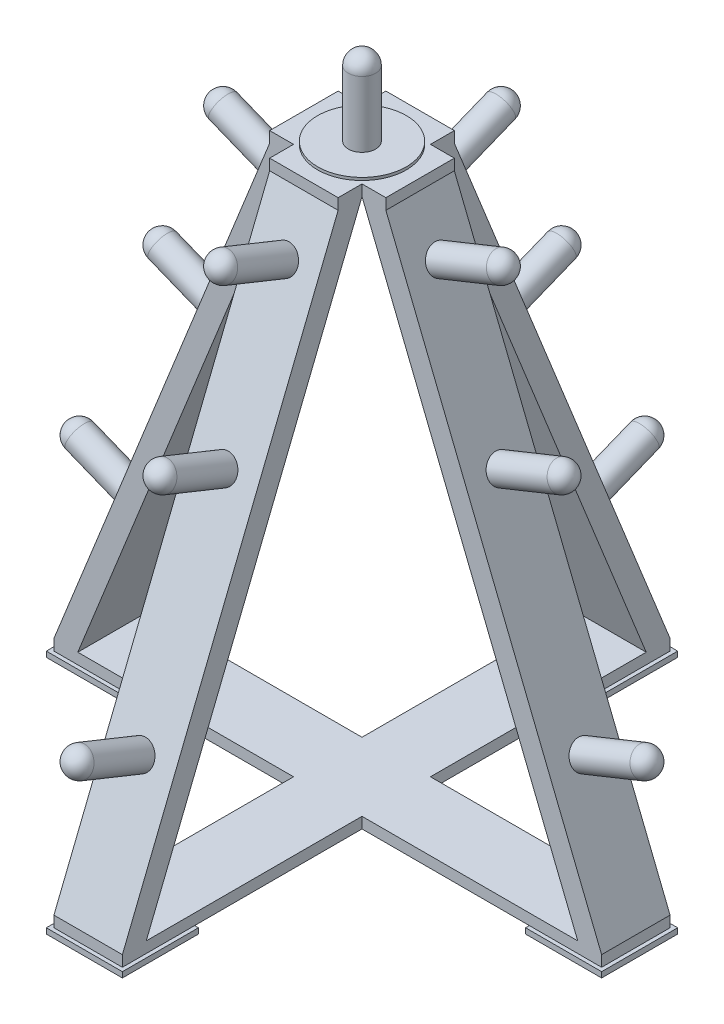
SolidWorks part; units mm, degrees
ref_plane "Front Plane" through (0, 0, 0) normal (0, 0, 1) x (1, 0, 0)
ref_plane "Top Plane" through (0, 0, 0) normal (0, 1, 0) x (1, 0, 0)
ref_plane "Right Plane" through (0, 0, 0) normal (1, 0, 0) x (0, 0, -1)
sketch "Sketch1" plane through (0, 0, 0) normal (0, 1, 0) x (1, 0, 0)
  line L0 (500, 62.5) -> (62.5, 62.5)
  line L1 (-62.5, 500) -> (62.5, 500)
  line L2 (-62.5, 500) -> (-62.5, 62.5)
  line L3 (-62.5, -500) -> (62.5, -500)
  line L4 (62.5, 500) -> (62.5, 62.5)
  line L7 (500, 62.5) -> (500, -62.5)
  line L8 (500, -62.5) -> (62.5, -62.5)
  line L9 (-500, 62.5) -> (-500, -62.5)
  line L10 (-62.5, -62.5) -> (-500, -62.5)
  line L11 (-62.5, 62.5) -> (-500, 62.5)
  line L13 (-62.5, -62.5) -> (-62.5, -500)
  line L14 (62.5, -62.5) -> (62.5, -500)
  point P0 (0, 0)
  point P13 (500, 0)
  dimension "D1" = 125
  dimension "D2" = 1000
extrude "Boss-Extrude1" add sketch "Sketch1" along normal blind 20
ref_plane "Plane1" through (0, 1000, 0) normal (0, 1, 0) x (1, 0, 0)
sketch "Sketch2" plane through (0, 1000, 0) normal (0, 1, 0) x (1, 0, 0)
  line L0 (-62.5, 106.087) -> (-62.5, 62.5)
  line L1 (-62.5, 500) -> (-62.5, 62.5) construction
  line L2 (-62.5, 62.5) -> (-106.087, 62.5)
  line L3 (-62.5, 62.5) -> (-500, 62.5) construction
  line L4 (-106.087, 62.5) -> (-106.087, -62.5)
  line L5 (-500, -62.5) -> (-62.5, -62.5) construction
  line L6 (-106.087, -62.5) -> (-62.5, -62.5)
  line L7 (-62.5, -62.5) -> (-62.5, -106.087)
  line L8 (-62.5, -62.5) -> (-62.5, -500) construction
  line L9 (-62.5, -106.087) -> (62.5, -106.087)
  line L10 (62.5, -500) -> (62.5, -62.5) construction
  line L11 (62.5, -106.087) -> (62.5, -62.5)
  line L12 (62.5, -62.5) -> (106.087, -62.5)
  line L13 (62.5, -62.5) -> (500, -62.5) construction
  line L14 (106.087, -62.5) -> (106.087, 62.5)
  line L15 (500, 62.5) -> (62.5, 62.5) construction
  line L16 (106.087, 62.5) -> (62.5, 62.5)
  line L17 (62.5, 62.5) -> (62.5, 106.087)
  line L18 (62.5, 62.5) -> (62.5, 500) construction
  line L19 (62.5, 106.087) -> (-62.5, 106.087)
sketch "Sketch3" plane through (0, 20, 0) normal (0, 1, 0) x (1, 0, 0)
  line L0 (-500, -62.5) -> (-62.5, -62.5) construction
  line L1 (-500, 62.5) -> (-456.413, 62.5)
  line L2 (-500, 62.5) -> (-500, -62.5)
  line L3 (-500, -62.5) -> (-456.413, -62.5)
  line L4 (-456.413, 62.5) -> (-456.413, -62.5)
  line L6 (-62.5, 62.5) -> (-106.087, 62.5) construction
extrude "Boss-Extrude2" add sketch "Sketch2" along normal blind 20 separate body
sketch "Sketch4" plane through (0, 1000, 0) normal (0, 1, 0) x (1, 0, 0)
  line L1 (-106.087, 62.5) -> (-62.5, 62.5)
  line L2 (-106.087, 62.5) -> (-106.087, -62.5)
  line L3 (-106.087, -62.5) -> (-62.5, -62.5)
  line L4 (-62.5, 62.5) -> (-62.5, -62.5)
sketch "Sketch5" plane through (0, 0, 0) normal (0, 0, 1) x (1, 0, 0)
  line L0 (-478.2065, 20) -> (-84.2935, 1000)
  line L1 (-500, 20) -> (-456.413, 20) construction
  line L2 (-106.087, 1000) -> (-62.5, 1000) construction
sweep "Sweep1" add profiles "Sketch4" path "Sketch5"
sketch "Sketch6" plane through (0, 0, 0) normal (0, 1, 0) x (1, 0, 0)
  line L0 (-478.2065, 62.5) -> (-478.2065, -62.5) construction
  line L1 (-500, 62.5) -> (-456.413, 62.5) construction
  line L2 (-500, -62.5) -> (-456.413, -62.5) construction
  line L3 (-500, 0) -> (-456.413, 0) construction
  line L4 (-500, 62.5) -> (-500, -62.5) construction
  line L5 (-456.413, 62.5) -> (-456.413, -62.5) construction
  circle A0 centre (0, 0) radius 478.2065
  point P14 (-478.2065, 0)
mirror "Mirror1" about plane through (0, 0, 0) normal (1, 0, 0) of "Sweep1"
sketch "Sketch7" plane through (0, 20, 0) normal (0, 1, 0) x (1, 0, 0)
  line L0 (199.9512, 199.9512) -> (-211.2774, -211.2774) construction
ref_plane "Plane2" through (0, 0, 0) normal (-0.7071, 0, -0.7071) x (-0.7071, 0, 0.7071)
mirror "Mirror2" about plane through (0, 0, 0) normal (-0.7071, 0, -0.7071) of "Sweep1"
mirror "Mirror3" about plane through (0, 0, 0) normal (0, 0, 1) of "Mirror2"
sketch "Sketch8" plane through (0, 175.8035, 437.3745) normal (0, 0.373, 0.9279) x (1, 0, 0)
  line L2 (0, 87.719) -> (0, -167.9187) construction
  line L3 (-62.5, -167.9187) -> (62.5, -167.9187) construction
  circle A0 centre (0, 493.5521) radius 25
  circle A1 centre (0, 87.719) radius 25
  circle A2 centre (0, 790.6314) radius 25
  point P4 (0, 523.769)
  point P11 (0, 501.454)
  point P12 (0, 493.5521)
  dimension "D1" = 50
extrude "Boss-Extrude3" add sketch "Sketch8" along normal blind 120
sketch "Sketch9" plane through (0, 220.5577, 548.7166) normal (0, 0.373, 0.9279) x (1, 0, 0)
  line L0 (-25, 493.5521) -> (25, 493.5521)
  circle A1 centre (0, 493.5521) radius 25
  arc A2 (25, 493.5521) -> (-25, 493.5521) centre (0, 493.5521) ccw
  dimension "D1" = 0
revolve "Revolve1" add sketch "Sketch9" angle 360 about L0
sketch "Sketch10" plane through (0, 220.5577, 548.7166) normal (0, 0.373, 0.9279) x (1, 0, 0)
  line L0 (-25, 87.719) -> (25, 87.719)
  circle A1 centre (0, 87.719) radius 25
  arc A2 (25, 87.719) -> (-25, 87.719) centre (0, 87.719) ccw
  dimension "D1" = 0
revolve "Revolve2" add sketch "Sketch10" angle 360 about L0
sketch "Sketch11" plane through (0, 0, 0) normal (0, -1, 0) x (1, 0, 0)
  line L0 (-62.5, 500) -> (62.5, 500) construction
  line L1 (-69.4271, 506.9271) -> (69.4271, 506.9271)
  line L2 (-69.4271, 506.9271) -> (-69.4271, 368.0729)
  line L3 (-69.4271, 368.0729) -> (69.4271, 368.0729)
  line L4 (69.4271, 506.9271) -> (69.4271, 368.0729)
  line L5 (-69.4271, 506.9271) -> (69.4271, 368.0729) construction
  line L6 (-69.4271, 368.0729) -> (69.4271, 506.9271) construction
  point P0 (0, 437.5)
  point P8 (0, 500)
extrude "Boss-Extrude4" add sketch "Sketch11" along normal blind 10
sketch "Sketch12" plane through (0, 1020, 0) normal (0, 1, 0) x (1, 0, 0)
  circle A0 centre (0, 0) radius 81
  dimension "D1" = 162
extrude "Boss-Extrude5" add sketch "Sketch12" along normal blind 5
sketch "Sketch13" plane through (0, 1025, 0) normal (0, 1, 0) x (1, 0, 0)
  circle A0 centre (0, 0) radius 25
  dimension "D1" = 50
extrude "Boss-Extrude6" add sketch "Sketch13" along normal blind 120
sketch "Sketch14" plane through (0, 1145, 0) normal (0, 1, 0) x (1, 0, 0)
  line L0 (-25, 0) -> (25, 0)
  circle A1 centre (0, 0) radius 25
  arc A2 (25, 0) -> (-25, 0) centre (0, 0) ccw
  dimension "D1" = 0
revolve "Revolve3" add sketch "Sketch14" angle 360 about L0
sketch "Sketch15" plane through (0, 220.5577, 548.7166) normal (0, 0.373, 0.9279) x (1, 0, 0)
  line L0 (-25, 790.6314) -> (25, 790.6314)
  circle A1 centre (0, 790.6314) radius 25
  arc A2 (25, 790.6314) -> (-25, 790.6314) centre (0, 790.6314) ccw
  dimension "D1" = 0
revolve "Revolve4" add sketch "Sketch15" angle 360 about L0
mirror "Mirror4" about plane through (0, 0, 0) normal (0, 0, 1) of "Revolve2", "Revolve4", "Revolve1", "Boss-Extrude4", "Boss-Extrude3"
mirror "Mirror5" about plane through (0, 0, 0) normal (-0.7071, 0, -0.7071) of "Boss-Extrude4", "Boss-Extrude3", "Revolve2", "Revolve4", "Revolve1"
mirror "Mirror6" about plane through (0, 0, 0) normal (1, 0, 0) of "Mirror5"
